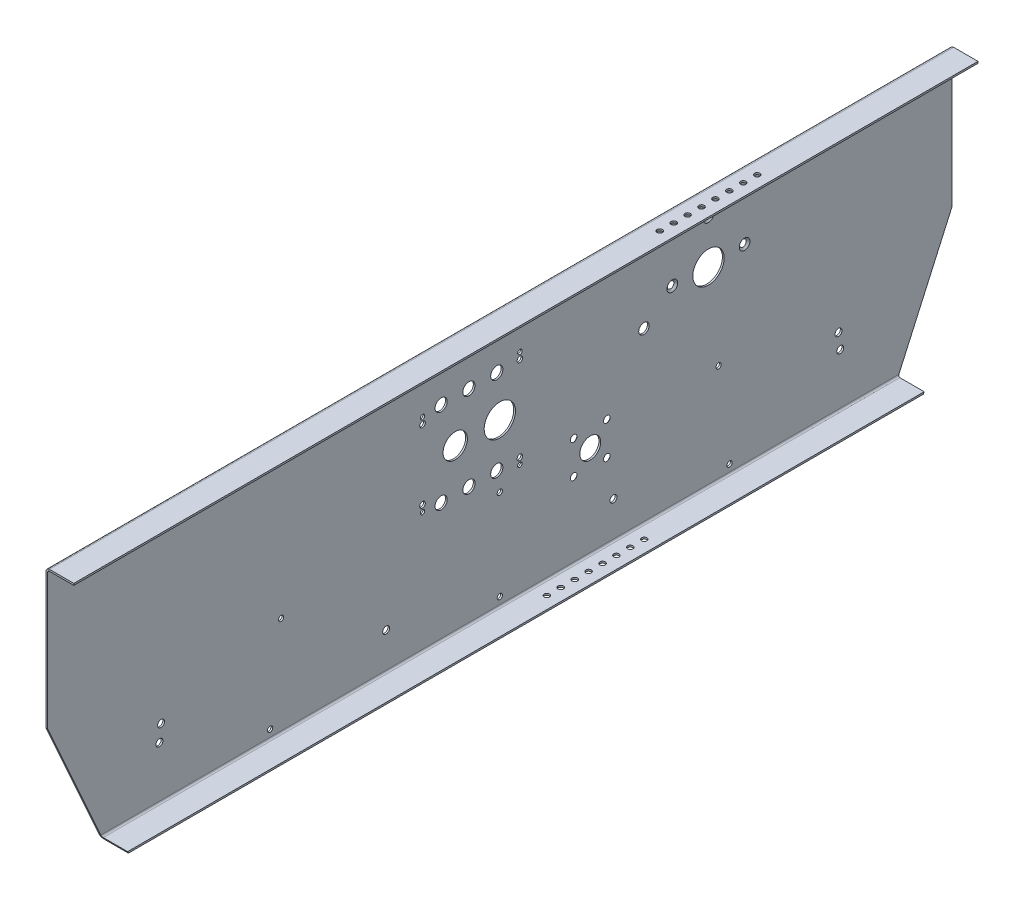
SolidWorks part; units mm, degrees
material "6061-T6 (SS)"
ref_plane "Front Plane" through (0, 0, 0) normal (0, 0, 1) x (1, 0, 0)
ref_plane "Top Plane" through (0, 0, 0) normal (0, 1, 0) x (1, 0, 0)
ref_plane "Right Plane" through (0, 0, 0) normal (1, 0, 0) x (0, 0, -1)
sketch "Sketch3" plane through (0, 0, 0) normal (0, 0, 1) x (1, 0, 0)
  line L0 (3.175, 233.4895) -> (25.4, 233.4895)
  line L1 (0, 231.902) -> (0, 0)
  line L4 (1.5875, 0) -> (1.5875, 231.902)
  line L5 (25.4, 233.4895) -> (25.4, 235.077)
  line L6 (25.4, 235.077) -> (3.175, 235.077)
  line L7 (0, 115.951) -> (26.891, 115.951) construction
  line L8 (25.4, -1.5875) -> (25.4, -3.175)
  line L9 (3.175, -1.5875) -> (25.4, -1.5875)
  line L10 (25.4, -3.175) -> (3.175, -3.175)
  arc A0 (0, 231.902) -> (3.175, 235.077) centre (3.175, 231.902) cw
  arc A1 (1.5875, 231.902) -> (3.175, 233.4895) centre (3.175, 231.902) cw
  arc A2 (0, 0) -> (3.175, -3.175) centre (3.175, 0) ccw
  arc A3 (1.5875, 0) -> (3.175, -1.5875) centre (3.175, 0) ccw
  dimension "D3" = 1.5875
  dimension "D4" = 1.5875
  dimension "D1" = 1.5875
  dimension "D2" = 231.902
  dimension "D5" = 25.4
base flange "Base-Flange2" sketch "Sketch3" thickness 825.5 reverse thickness direction no parameters "D1"=0.7366
sketch "Sketch1" plane through (0, 0, 0) normal (1, 0, 0) x (0, 0, -1)
  line L0 (0, 0) -> (825.5, 0) construction
  line L1 (407.3648, 6.35) -> (418.1352, 6.35) construction
  line L2 (825.5, 0) -> (825.5, 95.25) construction
  line L3 (0, 95.25) -> (825.5, 95.25) construction
  line L4 (0, 95.25) -> (0, 0) construction
  line L5 (622.4782, 0) -> (622.4782, 6.35) construction
  line L6 (-12.1207, 0) -> (-42.1566, 0) construction
  line L7 (-44.9273, -69.85) -> (939.266, -69.85) construction
  line L8 (825.5, -69.85) -> (825.5, 107.95) construction
  line L9 (308.991, 31.75) -> (516.509, 31.75) construction
  line L10 (219.9555, 31.75) -> (427.4735, 31.75) construction
  line L11 (516.509, 31.75) -> (722.0074, 60.6309) construction
  line L12 (308.991, 31.75) -> (103.4926, 60.6309) construction
  line L13 (412.75, 0) -> (412.75, 6.35) construction
  line L14 (412.75, 95.25) -> (412.75, 88.9) construction
  line L15 (612.4655, 95.25) -> (612.4655, 88.9) construction
  line L16 (614.8828, 6.35) -> (630.0737, 6.35) construction
  line L17 (600.5116, 88.9) -> (624.4194, 88.9) construction
  line L18 (203.0218, 0) -> (203.0218, 6.35) construction
  line L19 (195.4263, 6.35) -> (210.6172, 6.35) construction
  line L20 (213.0345, 95.25) -> (213.0345, 88.9) construction
  line L21 (308.991, 31.75) -> (101.9785, 46.2257) construction
  line L22 (516.509, 31.75) -> (723.5215, 46.2257) construction
  line L23 (201.0806, 88.9) -> (224.9884, 88.9) construction
  line L24 (1.8926, 60.6309) -> (386.0676, 60.6309) construction
  line L25 (372.0338, 146.002) -> (412.75, 146.002) construction
  line L26 (431.0621, 101.425) -> (431.0621, 107.267) construction
  line L27 (431.0621, 184.737) -> (431.0621, 190.579) construction
  line L28 (412.75, 146.002) -> (431.0621, 184.737) construction
  line L29 (412.75, 146.002) -> (431.0621, 107.267) construction
  line L30 (412.75, 146.002) -> (409.9801, 107.267) construction
  line L31 (412.75, 146.002) -> (409.9801, 184.737) construction
  line L32 (372.0338, 146.002) -> (384.5801, 184.737) construction
  line L33 (372.0338, 146.002) -> (359.1801, 184.737) construction
  line L34 (372.0338, 146.002) -> (359.1801, 107.267) construction
  line L35 (372.0338, 146.002) -> (384.5801, 107.267) construction
  line L36 (372.0338, 146.002) -> (342.1621, 114.252) construction
  line L37 (342.1621, 108.41) -> (342.1621, 114.252) construction
  line L38 (372.0338, 146.002) -> (342.1621, 177.752) construction
  line L39 (342.1621, 177.752) -> (342.1621, 183.594) construction
  line L40 (386.0676, 0) -> (386.0676, 95.25) construction
  line L41 (412.75, 0) -> (412.75, 31.75) construction
  line L42 (516.509, 31.75) -> (412.75, 146.002) construction
  line L43 (412.75, 146.002) -> (308.991, 31.75) construction
  line L44 (825.5, 231.902) -> (825.5, 0) construction
  line L45 (825.5, -3.175) -> (0, -3.175) construction
  line L46 (825.5, -3.175) -> (775.673, -3.175)
  line L47 (825.5, -3.175) -> (825.5, 107.95)
  line L48 (825.5, 107.95) -> (775.673, -3.175)
  line L49 (0, 107.95) -> (49.827, -3.175)
  line L50 (0, -3.175) -> (49.827, -3.175)
  line L51 (0, -3.175) -> (0, 107.95)
  line L52 (825.5, -3.175) -> (0, -3.175) construction
  line L53 (480.1426, 67.3925) -> (510.4575, 67.3925) construction
  line L54 (480.1426, 67.3925) -> (480.1426, 97.7074) construction
  line L55 (480.1426, 97.7074) -> (510.4575, 97.7074) construction
  line L56 (510.4575, 67.3925) -> (510.4575, 97.7074) construction
  line L57 (480.1426, 67.3925) -> (510.4575, 97.7074) construction
  line L58 (480.1426, 97.7074) -> (510.4575, 67.3925) construction
  line L59 (825.5, 0) -> (825.5, 231.902) construction
  line L60 (603.25, 171.6944) -> (603.25, 211.6845) construction
  line L61 (603.25, 171.6944) -> (570.2499, 173.1929) construction
  line L62 (603.25, 171.6944) -> (636.2501, 173.1929) construction
  line L63 (603.25, 171.6944) -> (495.3, 82.55) construction
  line L64 (472.0587, 110.6942) -> (580.0087, 199.8385) construction
  line L65 (518.5413, 54.4058) -> (626.4913, 143.5502) construction
  line L66 (825.5, 235.077) -> (0, 235.077) construction
  circle A0 centre (516.509, 31.75) radius 3.175
  circle A1 centre (308.991, 31.75) radius 3.175
  circle A2 centre (308.991, 31.75) radius 101.6 construction
  circle A3 centre (516.509, 31.75) radius 101.6 construction
  circle A4 centre (103.4926, 60.6309) radius 3.175
  circle A5 centre (722.0074, 60.6309) radius 3.175
  circle A6 centre (722.0074, 60.6309) radius 101.6 construction
  circle A7 centre (103.4926, 60.6309) radius 101.6 construction
  circle A8 centre (412.75, 6.35) radius 2.413
  circle A9 centre (412.75, 88.9) radius 2.413
  circle A10 centre (622.4782, 6.35) radius 2.413
  circle A11 centre (612.4655, 88.9) radius 2.413
  circle A12 centre (203.0218, 6.35) radius 2.413
  circle A13 centre (101.9785, 46.2257) radius 3.175
  circle A14 centre (101.9785, 46.2257) radius 101.6 construction
  circle A15 centre (723.5215, 46.2257) radius 3.175
  circle A16 centre (723.5215, 46.2257) radius 101.6 construction
  circle A17 centre (213.0345, 88.9) radius 2.413
  circle A18 centre (213.0345, 88.9) radius 4.7625 construction
  circle A19 centre (722.0074, 60.6309) radius 36.5 construction
  circle A20 centre (516.509, 31.75) radius 36.5 construction
  circle A21 centre (308.991, 31.75) radius 36.5 construction
  circle A22 centre (103.4926, 60.6309) radius 36.5 construction
  circle A23 centre (372.0338, 146.002) radius 21 construction
  circle A24 centre (359.1801, 107.267) radius 5.5562
  circle A25 centre (342.1621, 114.252) radius 2.5527
  circle A26 centre (342.1621, 108.41) radius 2.0447
  circle A27 centre (342.1621, 177.752) radius 2.5527
  circle A28 centre (342.1621, 183.594) radius 2.0447
  circle A29 centre (359.1801, 184.737) radius 5.5562
  circle A30 centre (384.5801, 184.737) radius 5.5563
  circle A31 centre (409.9801, 184.737) radius 5.5563
  circle A32 centre (431.0621, 184.737) radius 2.5527
  circle A33 centre (431.0621, 190.579) radius 2.0447
  circle A34 centre (431.0621, 107.267) radius 2.5527
  circle A35 centre (431.0621, 101.425) radius 2.0447
  circle A36 centre (412.75, 146.002) radius 14.2812
  circle A37 centre (372.0338, 146.002) radius 11.1061
  circle A38 centre (384.5801, 107.267) radius 5.5562
  circle A39 centre (409.9801, 107.267) radius 5.5562
  circle A40 centre (412.75, 146.002) radius 21 construction
  circle A41 centre (480.1426, 67.3925) radius 1.5875
  circle A42 centre (510.4575, 67.3925) radius 1.5875
  circle A43 centre (510.4575, 97.7074) radius 1.5875
  circle A44 centre (480.1426, 97.7074) radius 1.5875
  circle A45 centre (495.3, 82.55) radius 9.525
  circle A46 centre (636.2501, 173.1929) radius 1.27
  circle A47 centre (603.25, 171.6944) radius 14.2875
  circle A48 centre (570.2499, 173.1929) radius 1.27
  circle A49 centre (495.3, 82.55) radius 36.5 construction
  circle A50 centre (603.25, 211.6845) radius 1.27
  circle A51 centre (603.25, 171.6944) radius 36.5 construction
  circle A52 centre (544.3185, 152.527) radius 13.755 construction
  circle A53 centre (544.3185, 152.527) radius 4.7625
  point P16 (419.9974, 0)
  point P17 (412.75, 31.75)
  point P18 (419.9974, 0)
  point P21 (412.75, 31.75)
  point P32 (516.509, 28.575)
  point P33 (516.509, 34.925)
  point P34 (722.0074, 63.8059)
  point P35 (722.0074, 57.4559)
  point P36 (405.5026, 0)
  point P43 (388.3025, 95.25)
  point P44 (437.1975, 95.25)
  point P116 (801.073, -3.175)
  point P119 (775.673, -3.175)
  point P125 (495.3, 82.55)
  dimension "D3" = 207.518
  dimension "D5" = 203.2
  dimension "D4" = 6.35
  dimension "D10" = 63.5
  dimension "D15" = 4.826
  dimension "D18" = 6.35
  dimension "D21" = 4
  dimension "D22" = 101.9785
  dimension "D23" = 9.525
  dimension "D24" = 73
  dimension "D26" = 42
  dimension "D42" = 22.2123
  dimension "D43" = 11.1125
  dimension "D44" = 40.7162
  dimension "D47" = 5.1054
  dimension "D48" = 4.0894
  dimension "D50" = 28.5623
  dimension "D51" = 42
  dimension "D58" = 3.175
  dimension "D59" = 19.05
  dimension "D61" = 33.0341
  dimension "D62" = 28.575
  dimension "D63" = 2.54
  dimension "D64" = 87.4
  dimension "D66" = 73
  dimension "D67" = 73
  dimension "D68" = 139.9997
  dimension "D70" = 27.51
  dimension "D71" = 9.525
  dimension "D2" = 6.35
  dimension "D6" = 8
  dimension "D7" = 8
  dimension "D8" = 154.3355
  dimension "D9" = 31.75
  dimension "D11" = 177.8
  dimension "D12" = 6.35
  dimension "D13" = 25.4
  dimension "D14" = 6.35
  dimension "D16" = 6.35
  dimension "D17" = 6.35
  dimension "D19" = 48.8951
  dimension "D20" = 4
  dimension "D25" = 384.175
  dimension "D27" = 43.5934
  dimension "D28" = 46.746
  dimension "D29" = 5.842
  dimension "D30" = 136.746
  dimension "D31" = 46.746
  dimension "D32" = 24.896
  dimension "D33" = 36.305
  dimension "D34" = 36.305
  dimension "D35" = 24.896
  dimension "D36" = 40.812
  dimension "D37" = 85.91
  dimension "D38" = 85.91
  dimension "D39" = 29.393
  dimension "D40" = 29.393
  dimension "D41" = 40.7162
  dimension "D45" = 38.8339
  dimension "D46" = 28.5643
  dimension "D49" = 5.842
  dimension "D52" = 154.697
  dimension "D53" = 154.697
  dimension "D54" = 136.746
  dimension "D55" = 30.3149
  dimension "D56" = 85.725
  dimension "D57" = 330.2
  dimension "D60" = 39.9901
  dimension "D65" = 87.4
  dimension "D69" = 222.25
  dimension "D72" = 82.55
  dimension "D73" = 281.1815
sketch "Bend-Lines3" plane through (0, 0, 0) normal (0, 1, 0) x (1, 0, 0)
sketch "Bounding-Box3" plane through (0, 0, 0) normal (0, 1, 0) x (1, 0, 0)
extrude "Cut-Extrude3" cut sketch "Sketch1" along normal through all normal cut yes
hole_wizard "CSK for #10 Flat Head Machine Screw (100)2" positions "Sketch7" profile "Sketch6" countersink size "#10" standard "ANSI Inch" end condition through all
sketch "Sketch7" plane through (0, 0, 0) normal (-1, 0, 0) x (0, 0, 1)
  point P0 (-510.4575, 97.7074)
  point P3 (-480.1426, 97.7074)
  point P6 (-480.1426, 67.3925)
  point P9 (-510.4575, 67.3925)
sketch "Sketch6" plane through (0, 97.7074, -510.4575) normal (0, 1, 0) x (0, 0, 1)
  line L0 (0, 0) -> (0, 25.4)
  line L1 (0, 25.4) -> (2.4892, 25.4)
  line L2 (2.4892, 25.4) -> (2.4892, 2.0141)
  line L3 (2.4892, 2.0141) -> (4.8895, 0)
  line L5 (4.8895, 0) -> (0, 0)
  line L6 (-2.4892, 2.0141) -> (-4.8895, 0) construction
  line L11 (0, -6.35) -> (0, 107.95) construction
  dimension "Thru Hole Dia." = 4.9784
  dimension "Thru Hole Depth" = 25.4
  dimension "Near C'Sink Dia." = 9.779
  dimension "Near C'Sink Angle" = 100
hole_wizard "CSK for #10 Flat Head Machine Screw (100)3" positions "Sketch9" profile "Sketch8" countersink size "#10" standard "ANSI Inch" end condition through all
sketch "Sketch9" plane through (1.5875, 0, 0) normal (1, 0, 0) x (0, 0, -1)
  point P6 (603.25, 211.6845)
  point P11 (636.2501, 173.1929)
  point P14 (570.2499, 173.1929)
sketch "Sketch8" plane through (1.5875, 211.6845, -603.25) normal (0, 1, 0) x (0, 0, -1)
  line L0 (0, 0) -> (0, 1.5875)
  line L1 (0, 1.5875) -> (2.4892, 1.5875)
  line L2 (2.4892, 1.5875) -> (2.4892, 2.0141)
  line L3 (2.4892, 2.0141) -> (4.8895, 0)
  line L5 (4.8895, 0) -> (0, 0)
  line L6 (-2.4892, 2.0141) -> (-4.8895, 0) construction
  line L11 (0, -6.35) -> (0, 107.95) construction
  dimension "Thru Hole Dia." = 4.9784
  dimension "Thru Hole Depth" = 1.5875
  dimension "Near C'Sink Dia." = 9.779
  dimension "Near C'Sink Angle" = 100
sketch "Sketch10" plane through (0, -1.5875, 0) normal (0, 1, 0) x (1, 0, 0)
  line L0 (3.175, 417.619) -> (25.4, 417.619) construction
  line L1 (3.175, 776.3848) -> (3.175, 49.1152) construction
  line L2 (25.4, 776.3848) -> (25.4, 49.1152) construction
  line L3 (25.4, 776.3848) -> (3.175, 776.3848) construction
  line L4 (14.2875, 417.619) -> (14.2875, 443.019) construction
  line L5 (14.2875, 531.919) -> (14.2875, 443.019) construction
  line L6 (14.2875, 519.219) -> (14.2875, 531.919) construction
  circle A0 centre (14.2875, 443.019) radius 0.635
  circle A1 centre (14.2875, 455.719) radius 0.635
  circle A2 centre (14.2875, 468.419) radius 0.635
  circle A3 centre (14.2875, 481.119) radius 0.635
  circle A4 centre (14.2875, 493.819) radius 0.635
  circle A5 centre (14.2875, 506.519) radius 0.635
  circle A6 centre (14.2875, 519.219) radius 0.635
  circle A7 centre (14.2875, 531.919) radius 0.635
  dimension "D3" = 1.27
  dimension "D1" = 358.7658
  dimension "D2" = 25.4
  dimension "D5" = 12.7
  dimension "D4" = 8
extrude "Cut-Extrude4" cut sketch "Sketch10" against normal through all normal cut yes
hole_wizard "#8 Clearance Hole1" positions "Sketch12" profile "Sketch11" hole size "#8" standard "ANSI Inch" end condition through all
sketch "Sketch12" plane through (0, -1.5875, 0) normal (0, 1, 0) x (1, 0, 0)
  point P0 (14.2875, 531.919)
  point P3 (14.2875, 519.219)
  point P6 (14.2875, 506.519)
  point P9 (14.2875, 493.819)
  point P12 (14.2875, 481.119)
  point P15 (14.2875, 468.419)
  point P18 (14.2875, 455.719)
  point P21 (14.2875, 443.019)
sketch "Sketch11" plane through (14.2875, -1.5875, -531.919) normal (1, 0, 0) x (0, 0, 1)
  line L0 (0, 0) -> (0, 1.5875)
  line L1 (0, 1.5875) -> (2.4574, 1.5875)
  line L2 (2.4574, 1.5875) -> (2.4574, 0)
  line L5 (2.4574, 0) -> (0, 0)
  line L11 (0, -6.35) -> (0, 107.95) construction
  dimension "Thru Hole Dia." = 4.9149
  dimension "Thru Hole Depth" = 1.5875
sketch "Sketch13" plane through (0, 233.4895, 0) normal (0, -1, 0) x (1, 0, 0)
  line L0 (3.175, -546.1) -> (25.4, -546.1) construction
  line L1 (3.175, -825.5) -> (3.175, 0) construction
  line L2 (25.4, -825.5) -> (25.4, 0) construction
  line L3 (3.175, -825.5) -> (25.4, -825.5) construction
  circle A0 centre (14.2875, -546.1) radius 0.635
  circle A1 centre (14.2875, -558.8) radius 0.635
  circle A2 centre (14.2875, -571.5) radius 0.635
  circle A3 centre (14.2875, -584.2) radius 0.635
  circle A4 centre (14.2875, -596.9) radius 0.635
  circle A5 centre (14.2875, -609.6) radius 0.635
  circle A6 centre (14.2875, -622.3) radius 0.635
  circle A7 centre (14.2875, -635) radius 0.635
  dimension "D2" = 1.27
  dimension "D1" = 279.4
  dimension "D3" = 8
hole_wizard "#8 Clearance Hole2" positions "Sketch15" profile "Sketch14" hole size "#8" standard "ANSI Inch" end condition through all
sketch "Sketch15" plane through (0, 233.4895, 0) normal (0, -1, 0) x (-1, 0, 0)
  point P0 (-14.2875, 558.8)
  point P3 (-14.2875, 546.1)
  point P6 (-14.2875, 571.5)
  point P9 (-14.2875, 584.2)
  point P12 (-14.2875, 596.9)
  point P15 (-14.2875, 609.6)
  point P18 (-14.2875, 622.3)
  point P21 (-14.2875, 635)
sketch "Sketch14" plane through (14.2875, 233.4895, -558.8) normal (1, 0, 0) x (0, 0, -1)
  line L0 (0, 0) -> (0, 1.5875)
  line L1 (0, 1.5875) -> (2.4574, 1.5875)
  line L2 (2.4574, 1.5875) -> (2.4574, 0)
  line L5 (2.4574, 0) -> (0, 0)
  line L11 (0, -6.35) -> (0, 107.95) construction
  dimension "Thru Hole Dia." = 4.9149
  dimension "Thru Hole Depth" = 1.5875
sheet metal parameters "Sheet-Metal3" thickness 825.5 parameters "D1"=0.7366, "D7"=685.8
flat pattern "Flat-Pattern3"
sketch "Bend-Lines4" plane through (0, 0, 0) normal (0, 1, 0) x (1, 0, 0)
sketch3d "Bounding-Box4"
  line L0 (22.2247, -3.175, 0) -> (22.225, 235.077, 0) construction
  line L1 (-3.175, -3.175, 0) -> (-3.1747, 235.077, 0) construction
  line L2 (22.2247, -3.175, 0) -> (-3.175, -3.175, 0) construction
  line L3 (22.225, 235.077, 0) -> (-3.1747, 235.077, 0) construction
